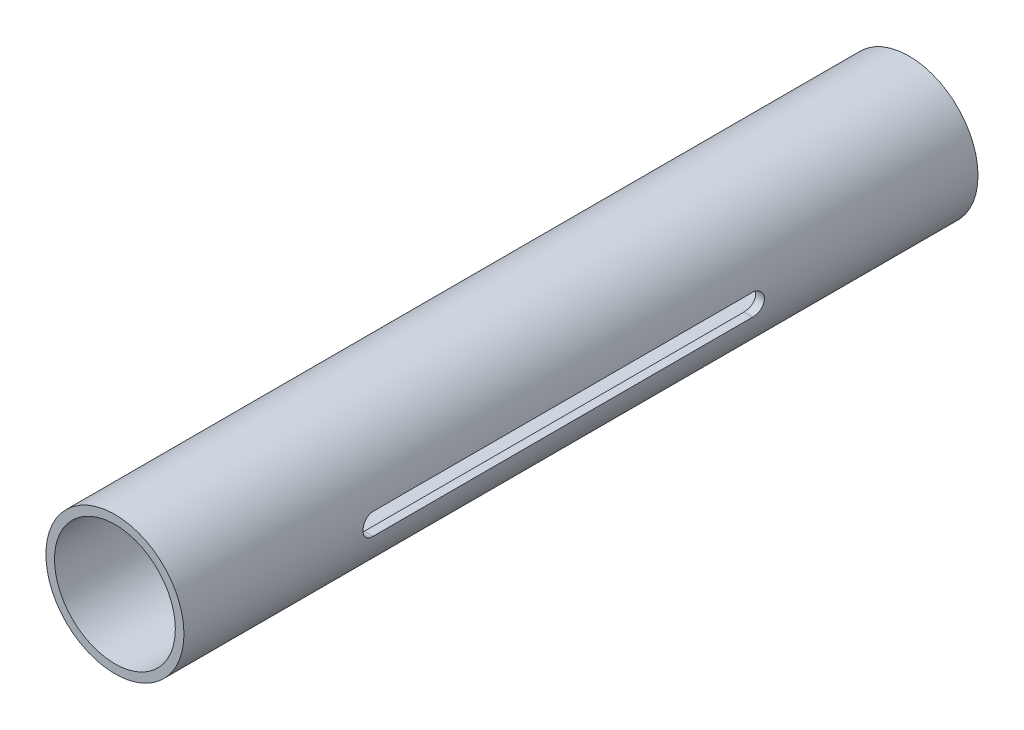
SolidWorks part; units mm, degrees
ref_plane "Front Plane" through (0, 0, 0) normal (0, 0, 1) x (1, 0, 0)
ref_plane "Top Plane" through (0, 0, 0) normal (0, 1, 0) x (1, 0, 0)
ref_plane "Right Plane" through (0, 0, 0) normal (1, 0, 0) x (0, 0, -1)
sketch "Sketch1" plane through (0, 0, 0) normal (0, 0, 1) x (1, 0, 0)
  line L0 (-25.4, 0) -> (-22.225, 0) construction
  circle A0 centre (0, 0) radius 22.225 construction
  circle A1 centre (0, 0) radius 25.4 construction
  dimension "OD" = 50.8
  dimension "ID" = 44.45
  dimension "Wall Thickness" = 3.175
sketch "Sketch2" plane through (0, 0, 0) normal (1, 0, 0) x (0, 0, -1)
  line L0 (-152.4, -25.4) -> (152.4, -25.4) construction
  point P2 (0, -25.4)
  point P3 (76.2, -25.4)
  point P4 (-76.2, -25.4)
  dimension "Length" = 304.8
  dimension "D1" = 76.2
  dimension "D2" = 76.2
sketch "Sketch3" plane through (0, 0, 0) normal (0, 0, 1) x (1, 0, 0)
  circle A0 centre (0, 0) radius 22.225 construction
  circle A1 centre (0, 0) radius 25.4 construction
  circle A2 centre (0, 0) radius 22.225
  circle A3 centre (0, 0) radius 25.4
extrude "Boss-Extrude2" add sketch "Sketch3" along normal up to vertex (152.4 mm away) and the other way up to vertex (152.4 mm away) up to point (0, -25.4, 152.4) other way up to point (0, -25.4, -152.4)
sketch "Sketch4" plane through (0, 0, 152.4) normal (0, 0, 1) x (1, 0, 0)
  circle A0 centre (0, 0) radius 36.4857
extrude "Cut-Extrude1" cut sketch "Sketch4" against normal offset from surface (12.7 mm away) 12.7 up to face at (25.4, 0, 152.4)
sketch "Sketch5" plane through (0, 0, 0) normal (1, 0, 0) x (0, 0, -1)
  line L0 (0, 0) -> (69.85, 0) construction
  line L1 (0, 0) -> (-69.85, 0) construction
  line L2 (-139.7, 0) -> (152.4, 0) construction
  line L3 (152.4, -25.4) -> (152.4, 25.4) construction
  line L4 (-139.7, 25.4) -> (-139.7, -25.4) construction
  line L5 (-69.85, 3.9687) -> (69.85, 3.9687)
  line L6 (69.85, -3.9687) -> (-69.85, -3.9687)
  line L7 (0, 3.9687) -> (0, -3.9687) construction
  circle A0 centre (-69.85, 0) radius 3.9687 construction
  arc A2 (-69.85, 3.9687) -> (-69.85, -3.9687) centre (-69.85, 0) ccw
  circle A4 centre (69.85, 0) radius 3.9688 construction
  arc A5 (69.85, 3.9687) -> (69.85, -3.9687) centre (69.85, 0) cw
  point P13 (0, 3.9687)
  point P14 (0, -3.9687)
  point P17 (0, 0)
  dimension "D1" = 69.85
  dimension "D2" = 82.55
  dimension "D3" = 7.9375
extrude "Cut-Extrude2" cut sketch "Sketch5" against normal through all both and the other way through all
equation "\"D1@Sketch2\"=\"OD@Sketch1\"*1.5"
equation "\"D2@Sketch2\"=\"D1@Sketch2\""
